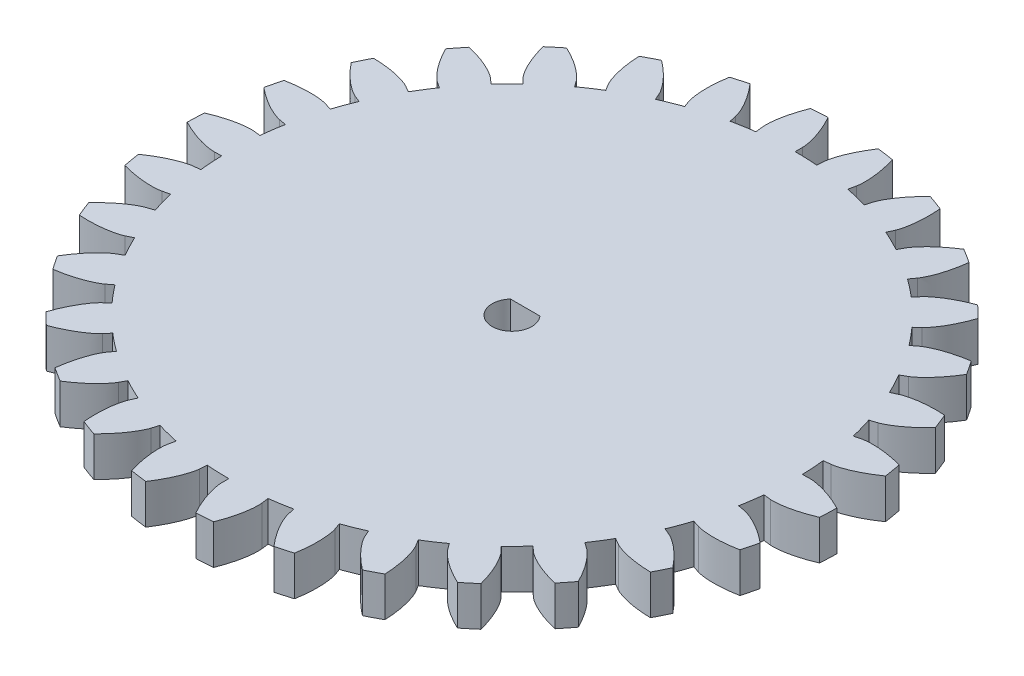
SolidWorks part; units mm, degrees
ref_plane "Front Plane" through (0, 0, 0) normal (0, 0, 1) x (1, 0, 0)
ref_plane "Top Plane" through (0, 0, 0) normal (0, 1, 0) x (1, 0, 0)
ref_plane "Right Plane" through (0, 0, 0) normal (1, 0, 0) x (0, 0, -1)
sketch "Reference attributes" plane through (0, 0, 0) normal (0, 1, 0) x (1, 0, 0)
  line L0 (0, 0) -> (30, 0) construction
  line L1 (0, -10) -> (1.56, -10) construction
  line L2 (0, 0) -> (28.9778, 7.7646) construction
  line L3 (0, 0) -> (28.1908, 10.2606) construction
  dimension "Teeth" = 30
  dimension "Module" = 1.56
  dimension "D2" = 10
  dimension "Helix Angle" = 15
  dimension "Pressure angle" = 20
sketch "Gear billet" plane through (0, 0, 0) normal (0, 1, 0) x (1, 0, 0)
  circle A0 centre (0, 0) radius 24.96
  dimension "OuterDi" = 49.92
extrude "Gear billet Extrude" add sketch "Gear billet" along normal blind 3
ref_plane "Opposite gear face" through (0, 3, 0) normal (0, 1, 0) x (1, 0, 0)
ref_point "Twist centre point top"
ref_point "Twist centre point bottom"
ref_axis "Axis" through (0, 3, 0) along (0, -1, 0)
sketch "Involute Profile" plane through (0, 3, 0) normal (0, 1, 0) x (1, 0, 0)
  line L0 (0, 0) -> (0, 21.9888) construction
  line L1 (0, 0) -> (1.7393, 21.9199) construction
  circle A0 centre (0, 0) radius 23.4
  circle A4 centre (0, 0) radius 21.9888 construction
  spline S0 degree 4 poles (0, 21.9888) (0, 22.0227) (-0.002, 22.0904) (-0.0183, 22.28) (-0.0768, 22.638) (-0.2134, 23.1773) (-0.4715, 23.897) (-0.8867, 24.788) (-1.4705, 25.7809) (-2.2091, 26.8084) (-3.0996, 27.8414) (-4.0685, 28.8009) (-5.1038, 29.688) (-6.2499, 30.5444) (-7.7363, 31.5083) (-9.5978, 32.5098) (-11.8594, 33.4668) (-14.465, 34.2773) (-17.1335, 34.8452) (-19.8405, 35.1813) (-22.5656, 35.2961) (-25.2912, 35.1997) (-27.663, 34.9395) (-29.6787, 34.5969) (-31.3427, 34.2349) (-32.4991, 33.942) (-33.4813, 33.6643) (-34.2972, 33.414) (-34.9416, 33.2053) (-35.5928, 32.9818) (-36.2216, 32.756) (-36.8226, 32.5279) (-37.3087, 32.3371) (-37.8607, 32.1112) (-38.2165, 31.9615) (-38.789, 31.7141) (-39.2308, 31.5139) (-39.7658, 31.2673) (-40.2388, 31.0393) (-40.7468, 30.7895) (-41.2252, 30.5448) (-41.5991, 30.3497) (-41.8363, 30.2223) (-41.9593, 30.1561) knots 0 0 0 0 0 0.002802 0.005604 0.015718 0.02996 0.048734 0.068727 0.096889 0.125051 0.153212 0.181374 0.209535 0.237696 0.271429 0.327752 0.384075 0.440398 0.496721 0.553044 0.609367 0.66569 0.722013 0.750174 0.778336 0.806497 0.820578 0.834659 0.84874 0.86282 0.876901 0.890982 0.900036 0.909091 0.920455 0.931818 0.943182 0.954545 0.965909 0.977273 0.988636 1 1 1 1 1 construction
  spline S1 degree 4 poles (0, 21.9888) (0, 22.0227) (-0.002, 22.0904) (-0.0183, 22.28) (-0.0768, 22.638) (-0.2134, 23.1773) (-0.4715, 23.897) (-0.8867, 24.788) (-1.4705, 25.7809) (-2.2091, 26.8084) (-3.0996, 27.8414) (-4.0685, 28.8009) (-5.1038, 29.688) (-6.2499, 30.5444) (-7.7363, 31.5083) (-9.5978, 32.5098) (-11.8594, 33.4668) (-14.465, 34.2773) (-17.1335, 34.8452) (-19.8405, 35.1813) (-22.5656, 35.2961) (-25.2912, 35.1997) (-27.663, 34.9395) (-29.6787, 34.5969) (-31.3427, 34.2349) (-32.4991, 33.942) (-33.4813, 33.6643) (-34.2972, 33.414) (-34.9416, 33.2053) (-35.5928, 32.9818) (-36.2216, 32.756) (-36.8226, 32.5279) (-37.3087, 32.3371) (-37.7167, 32.1701) (-37.9021, 32.0931) (-37.9939, 32.0546) knots 0 0 0 0 0 0.002802 0.005604 0.015718 0.02996 0.048734 0.068727 0.096889 0.125051 0.153212 0.181374 0.209535 0.237696 0.271429 0.327752 0.384075 0.440398 0.496721 0.553044 0.609367 0.66569 0.722013 0.750174 0.778336 0.806497 0.820578 0.834659 0.84874 0.86282 0.876901 0.890982 0.900036 0.909091 0.909091 0.909091 0.909091 0.909091
  spline S2 degree 4 poles (1.7393, 21.9199) (1.742, 21.9537) (1.7493, 22.0211) (1.7806, 22.2087) (1.8672, 22.561) (2.046, 23.0878) (2.3602, 23.7848) (2.8446, 24.6402) (3.5051, 25.5838) (4.3226, 26.5496) (5.2921, 27.509) (6.3339, 28.3888) (7.4361, 29.1913) (8.6463, 29.9544) (10.2043, 30.7977) (12.1392, 31.6487) (14.4694, 32.4239) (17.131, 33.0257) (19.836, 33.3808) (22.5612, 33.5017) (25.2867, 33.4006) (27.9962, 33.0889) (30.34, 32.6419) (32.3223, 32.141) (33.9524, 31.6485) (35.082, 31.2651) (36.0392, 30.9106) (36.8327, 30.5965) (37.4586, 30.3374) (38.0901, 30.0632) (38.699, 29.7884) (39.2801, 29.5134) (39.7496, 29.2848) (40.282, 29.0159) (40.6248, 28.8385) (41.176, 28.5466) (41.6005, 28.3121) (42.1144, 28.0239) (42.5679, 27.7593) (43.0545, 27.4701) (43.5121, 27.1883) (43.8694, 26.9642) (44.0957, 26.8185) (44.2131, 26.7428) knots 0 0 0 0 0 0.002802 0.005604 0.015718 0.02996 0.048734 0.068727 0.096889 0.125051 0.153212 0.181374 0.209535 0.237696 0.271429 0.327752 0.384075 0.440398 0.496721 0.553044 0.609367 0.66569 0.722013 0.750174 0.778336 0.806497 0.820578 0.834659 0.84874 0.86282 0.876901 0.890982 0.900036 0.909091 0.920455 0.931818 0.943182 0.954545 0.965909 0.977273 0.988636 1 1 1 1 1 construction
  spline S3 degree 4 poles (1.7393, 21.9199) (1.742, 21.9537) (1.7493, 22.0211) (1.7806, 22.2087) (1.8672, 22.561) (2.046, 23.0878) (2.3602, 23.7848) (2.8446, 24.6402) (3.5051, 25.5838) (4.3226, 26.5496) (5.2921, 27.509) (6.3339, 28.3888) (7.4361, 29.1913) (8.6463, 29.9544) (10.2043, 30.7977) (12.1392, 31.6487) (14.4694, 32.4239) (17.131, 33.0257) (19.836, 33.3808) (22.5612, 33.5017) (25.2867, 33.4006) (27.9962, 33.0889) (30.34, 32.6419) (32.3223, 32.141) (33.9524, 31.6485) (35.082, 31.2651) (36.0392, 30.9106) (36.8327, 30.5965) (37.4586, 30.3374) (38.0901, 30.0632) (38.699, 29.7884) (39.2801, 29.5134) (39.7496, 29.2848) (40.1431, 29.086) (40.3219, 28.9946) (40.4103, 28.9489) knots 0 0 0 0 0 0.002802 0.005604 0.015718 0.02996 0.048734 0.068727 0.096889 0.125051 0.153212 0.181374 0.209535 0.237696 0.271429 0.327752 0.384075 0.440398 0.496721 0.553044 0.609367 0.66569 0.722013 0.750174 0.778336 0.806497 0.820578 0.834659 0.84874 0.86282 0.876901 0.890982 0.900036 0.909091 0.909091 0.909091 0.909091 0.909091
  point P6 (-0.3003, 23.3981)
  point P11 (2.1501, 23.301)
  dimension "BaseDi" = 43.9776
  dimension "Adjusted Reference Diameter" = 46.8
  dimension "Reference Circumferential pitch" = 2.4504
sketch "Tooth profile" plane through (0, 3, 0) normal (0, 1, 0) x (1, 0, 0)
  line L0 (0, 0) -> (0, 21.9888) construction
  line L1 (0, 0) -> (1.7393, 21.9199) construction
  line L2 (0, 0) -> (0, 21.9888)
  line L3 (0, 0) -> (1.7393, 21.9199)
  line L4 (-0.2, -5.0491) -> (-0.2, 21.9888) construction
  line L5 (-0.2, -5.0491) -> (1.9386, 21.9041) construction
  circle A0 centre (0, 0) radius 24.96 construction
  circle A1 centre (0, 0) radius 24.96
  circle A2 centre (0, 0) radius 21.45
  spline S0 degree 1 poles (-0.2, 21.9888) (-37.9165, 31.8702) knots 0 0 1 1 construction
  spline S1 degree 4 poles (999.1982, -17.1121) (-36.277, 17.6441) (-0.8293, 18.6178) (0.2518, 20.6259) (-0.0768, 22.638) (-0.2134, 23.1773) (-0.4715, 23.897) (-0.8867, 24.788) (-1.4705, 25.7809) (-2.2091, 26.8084) (-3.0996, 27.8414) (-4.0685, 28.8009) (-5.1038, 29.688) (-6.2499, 30.5444) (-7.7363, 31.5083) (-9.5978, 32.5098) (-11.8594, 33.4668) (-14.465, 34.2773) (-17.1335, 34.8452) (-19.8405, 35.1813) (-22.5656, 35.2961) (-25.2912, 35.1997) (-27.663, 34.9395) (-29.6787, 34.5969) (-31.3427, 34.2349) (-32.4991, 33.942) (-33.4813, 33.6643) (-34.2972, 33.414) (-34.9416, 33.2053) (-35.5928, 32.9818) (-36.2216, 32.756) (-36.8226, 32.5279) (-38.6811, 31.7987) (-42.1779, 30.2496) (-10.1825, 43.4984) (-959.7925, -355.2431) knots -0.138436 -0.138436 -0.138436 -0.138436 -0.138436 0.002802 0.005604 0.015718 0.02996 0.048734 0.068727 0.096889 0.125051 0.153212 0.181374 0.209535 0.237696 0.271429 0.327752 0.384075 0.440398 0.496721 0.553044 0.609367 0.66569 0.722013 0.750174 0.778336 0.806497 0.820578 0.834659 0.84874 0.86282 0.876901 0.890982 0.900036 1.039722 1.039722 1.039722 1.039722 1.039722 only from (0, 21.9888) to (-37.9939, 32.0546) construction
  spline S2 degree 4 poles (-997.4211, 61.976) (37.5589, 14.7194) (2.2993, 18.4939) (1.3805, 20.5812) (1.8672, 22.561) (2.046, 23.0878) (2.3602, 23.7848) (2.8446, 24.6402) (3.5051, 25.5838) (4.3226, 26.5496) (5.2921, 27.509) (6.3339, 28.3888) (7.4361, 29.1913) (8.6463, 29.9544) (10.2043, 30.7977) (12.1392, 31.6487) (14.4694, 32.4239) (17.131, 33.0257) (19.836, 33.3808) (22.5612, 33.5017) (25.2867, 33.4006) (27.9962, 33.0889) (30.34, 32.6419) (32.3223, 32.141) (33.9524, 31.6485) (35.082, 31.2651) (36.0392, 30.9106) (36.8327, 30.5965) (37.4586, 30.3374) (38.0901, 30.0632) (38.699, 29.7884) (39.2801, 29.5134) (41.0751, 28.6395) (44.4385, 26.8186) (13.5912, 42.5567) (928.6863, -430.0476) knots -0.138436 -0.138436 -0.138436 -0.138436 -0.138436 0.002802 0.005604 0.015718 0.02996 0.048734 0.068727 0.096889 0.125051 0.153212 0.181374 0.209535 0.237696 0.271429 0.327752 0.384075 0.440398 0.496721 0.553044 0.609367 0.66569 0.722013 0.750174 0.778336 0.806497 0.820578 0.834659 0.84874 0.86282 0.876901 0.890982 0.900036 1.039722 1.039722 1.039722 1.039722 1.039722 only from (1.7393, 21.9199) to (40.4103, 28.9489) construction
  spline S3 degree 1 poles (1.9386, 21.9041) (40.3186, 28.7712) knots 0 0 1 1 construction
  spline S4 degree 4 poles (0, 21.9888) (0, 22.0227) (-0.002, 22.0904) (-0.0183, 22.28) (-0.0768, 22.638) (-0.2134, 23.1773) (-0.4715, 23.897) (-0.8867, 24.788) (-1.4705, 25.7809) (-2.2091, 26.8084) (-3.0996, 27.8414) (-4.0685, 28.8009) (-5.1038, 29.688) (-6.2499, 30.5444) (-7.7363, 31.5083) (-9.5978, 32.5098) (-11.8594, 33.4668) (-14.465, 34.2773) (-17.1335, 34.8452) (-19.8405, 35.1813) (-22.5656, 35.2961) (-25.2912, 35.1997) (-27.663, 34.9395) (-29.6787, 34.5969) (-31.3427, 34.2349) (-32.4991, 33.942) (-33.4813, 33.6643) (-34.2972, 33.414) (-34.9416, 33.2053) (-35.5928, 32.9818) (-36.2216, 32.756) (-36.8226, 32.5279) (-37.3087, 32.3371) (-37.7167, 32.1701) (-37.9021, 32.0931) (-37.9939, 32.0546) knots 0 0 0 0 0 0.002802 0.005604 0.015718 0.02996 0.048734 0.068727 0.096889 0.125051 0.153212 0.181374 0.209535 0.237696 0.271429 0.327752 0.384075 0.440398 0.496721 0.553044 0.609367 0.66569 0.722013 0.750174 0.778336 0.806497 0.820578 0.834659 0.84874 0.86282 0.876901 0.890982 0.900036 0.909091 0.909091 0.909091 0.909091 0.909091
  spline S5 degree 4 poles (1.7393, 21.9199) (1.742, 21.9537) (1.7493, 22.0211) (1.7806, 22.2087) (1.8672, 22.561) (2.046, 23.0878) (2.3602, 23.7848) (2.8446, 24.6402) (3.5051, 25.5838) (4.3226, 26.5496) (5.2921, 27.509) (6.3339, 28.3888) (7.4361, 29.1913) (8.6463, 29.9544) (10.2043, 30.7977) (12.1392, 31.6487) (14.4694, 32.4239) (17.131, 33.0257) (19.836, 33.3808) (22.5612, 33.5017) (25.2867, 33.4006) (27.9962, 33.0889) (30.34, 32.6419) (32.3223, 32.141) (33.9524, 31.6485) (35.082, 31.2651) (36.0392, 30.9106) (36.8327, 30.5965) (37.4586, 30.3374) (38.0901, 30.0632) (38.699, 29.7884) (39.2801, 29.5134) (39.7496, 29.2848) (40.1431, 29.086) (40.3219, 28.9946) (40.4103, 28.9489) knots 0 0 0 0 0 0.002802 0.005604 0.015718 0.02996 0.048734 0.068727 0.096889 0.125051 0.153212 0.181374 0.209535 0.237696 0.271429 0.327752 0.384075 0.440398 0.496721 0.553044 0.609367 0.66569 0.722013 0.750174 0.778336 0.806497 0.820578 0.834659 0.84874 0.86282 0.876901 0.890982 0.900036 0.909091 0.909091 0.909091 0.909091 0.909091
  spline S6 degree 3 poles (-37.9165, 31.8702) (-34.5637, 33.2771) (-29.2333, 34.7703) (-21.9373, 35.188) (-16.4816, 34.6386) (-11.2068, 33.1415) (-7.1485, 31.0333) (-4.2854, 28.7886) (-2.4032, 26.8185) (-1.144, 24.9283) (-0.5176, 23.4861) (-0.2764, 22.622) (-0.2, 22.203) (-0.2, 21.9888) knots 0 0 0 0 0.227273 0.340909 0.454545 0.568182 0.681818 0.738636 0.795455 0.852273 0.880682 0.894886 0.909091 0.909091 0.909091 0.909091 construction
  spline S7 degree 3 poles (1.9386, 21.9041) (1.9556, 22.1176) (2.0649, 22.5293) (2.3737, 23.3716) (3.1122, 24.7598) (4.5169, 26.5444) (6.5491, 28.3595) (9.5808, 30.3707) (13.7931, 32.1512) (19.1698, 33.2264) (24.6519, 33.3426) (31.892, 32.3491) (37.0876, 30.439) (40.3186, 28.7712) knots 0 0 0 0 0.014205 0.028409 0.056818 0.113636 0.170455 0.227273 0.340909 0.454545 0.568182 0.681818 0.909091 0.909091 0.909091 0.909091 construction
  dimension "RootDi" = 42.9
  dimension "Offset" = 0.2
extrude "Cut tooth profile" cut sketch "Tooth profile" against normal up to next contours A1 region at (0.9288, 3, -23.4481)
sketch "Tooth profile OFFSET" plane through (0, 3, 0) normal (0, 1, 0) x (1, 0, 0)
  line L4 (-0.1, -2.5246) -> (-0.1, 21.9888)
  line L5 (1.839, 21.912) -> (-0.1, -2.5246)
  line L6 (-0.1, -2.5246) -> (-0.1, 21.9888)
  line L7 (1.839, 21.912) -> (-0.1, -2.5246)
  circle A3 centre (0, 0) radius 24.96 construction
  circle A4 centre (0, 0) radius 24.96
  circle A6 centre (0, 0) radius 21.35
  circle A7 centre (0, 0) radius 21.35
  spline S4 degree 3 poles (1814.9164, -893.4497) (11.2099, 41.5431) (47.43, 25.2825) (39.9677, 29.0624) (39.857, 29.118) (39.5391, 29.276) (39.3439, 29.3707) (38.9333, 29.5665) (38.7217, 29.6655) (38.306, 29.8557) (38.0998, 29.9479) (37.053, 30.4066) (36.203, 30.7469) (33.6257, 31.6798) (31.8646, 32.1874) (28.2886, 32.9442) (26.4731, 33.1936) (22.8249, 33.4041) (20.9921, 33.3652) (17.3608, 32.9668) (15.562, 32.6072) (12.0726, 31.5326) (10.3808, 30.8175) (8.0112, 29.4496) (7.2497, 28.9445) (5.8069, 27.8305) (5.1252, 27.2218) (3.8784, 25.8951) (3.3115, 25.1772) (2.6029, 24.0143) (2.3903, 23.6123) (2.1256, 22.9877) (2.0464, 22.776) (1.9476, 22.4534) (1.918, 22.3451) (0.4034, 15.6952) (12.5067, 9.1011) (1949.2716, 476.354) knots -0.54262 -0.54262 -0.54262 -0.54262 0.007812 0.007812 0.015625 0.015625 0.03125 0.03125 0.046875 0.046875 0.0625 0.0625 0.125 0.125 0.25 0.25 0.375 0.375 0.5 0.5 0.625 0.625 0.75 0.75 0.8125 0.8125 0.875 0.875 0.9375 0.9375 0.96875 0.96875 0.984375 0.984375 0.992187 0.992187 1.461818 1.461818 1.461818 1.461818 only from (40.3645, 28.8601) to (1.839, 21.912)
  spline S5 degree 3 poles (-1905.5571, 629.0682) (-11.748, 10.0617) (0.8394, 15.6778) (-0.1445, 22.4268) (-0.1655, 22.5371) (-0.2385, 22.8665) (-0.3007, 23.0838) (-0.5151, 23.7274) (-0.6952, 24.1449) (-1.3097, 25.3602) (-1.818, 26.1208) (-2.956, 27.5419) (-3.5873, 28.2027) (-4.9375, 29.4272) (-5.6567, 29.991) (-7.9107, 31.542) (-9.5406, 32.3887) (-12.9341, 33.736) (-14.6989, 34.2367) (-18.2872, 34.9211) (-20.1112, 35.1048) (-23.7646, 35.1836) (-25.5942, 35.0786) (-29.2188, 34.607) (-31.0145, 34.2403) (-33.6576, 33.5142) (-34.5318, 33.2422) (-35.6116, 32.8677) (-35.8244, 32.7921) (-36.2539, 32.6354) (-36.4727, 32.5534) (-36.8975, 32.3907) (-37.0995, 32.3118) (-37.429, 32.1793) (-37.5437, 32.1327) (-45.2816, 28.9549) (-7.889, 42.2995) (-1879.8826, -747.087) knots -0.461823 -0.461823 -0.461823 -0.461823 0.007812 0.007812 0.015625 0.015625 0.03125 0.03125 0.0625 0.0625 0.125 0.125 0.1875 0.1875 0.25 0.25 0.375 0.375 0.5 0.5 0.625 0.625 0.75 0.75 0.875 0.875 0.9375 0.9375 0.953125 0.953125 0.96875 0.96875 0.984375 0.984375 0.992188 0.992188 1.542618 1.542618 1.542618 1.542618 only from (-0.1, 21.9888) to (-37.9552, 31.9624)
  spline S6 degree 3 poles (40.3645, 28.8601) (40.2722, 28.9077) (40.1765, 28.9566) (39.9677, 29.0624) (39.857, 29.118) (39.5391, 29.276) (39.3439, 29.3707) (38.9333, 29.5665) (38.7217, 29.6655) (38.306, 29.8557) (38.0998, 29.9479) (37.053, 30.4066) (36.203, 30.7469) (33.6257, 31.6798) (31.8646, 32.1874) (28.2886, 32.9442) (26.4731, 33.1936) (22.8249, 33.4041) (20.9921, 33.3652) (17.3608, 32.9668) (15.562, 32.6072) (12.0726, 31.5326) (10.3808, 30.8175) (8.0112, 29.4496) (7.2497, 28.9445) (5.8069, 27.8305) (5.1252, 27.2218) (3.8784, 25.8951) (3.3115, 25.1772) (2.6029, 24.0143) (2.3903, 23.6123) (2.1256, 22.9877) (2.0464, 22.776) (1.9476, 22.4534) (1.918, 22.3451) (1.8684, 22.1275) (1.8474, 22.0187) (1.839, 21.912) knots 0 0 0 0 0.007812 0.007812 0.015625 0.015625 0.03125 0.03125 0.046875 0.046875 0.0625 0.0625 0.125 0.125 0.25 0.25 0.375 0.375 0.5 0.5 0.625 0.625 0.75 0.75 0.8125 0.8125 0.875 0.875 0.9375 0.9375 0.96875 0.96875 0.984375 0.984375 0.992187 0.992187 1 1 1 1
  spline S7 degree 3 poles (-0.1, 21.9888) (-0.1, 22.0958) (-0.1123, 22.206) (-0.1445, 22.4268) (-0.1655, 22.5371) (-0.2385, 22.8665) (-0.3007, 23.0838) (-0.5151, 23.7274) (-0.6952, 24.1449) (-1.3097, 25.3602) (-1.818, 26.1208) (-2.956, 27.5419) (-3.5873, 28.2027) (-4.9375, 29.4272) (-5.6567, 29.991) (-7.9107, 31.542) (-9.5406, 32.3887) (-12.9341, 33.736) (-14.6989, 34.2367) (-18.2872, 34.9211) (-20.1112, 35.1048) (-23.7646, 35.1836) (-25.5942, 35.0786) (-29.2188, 34.607) (-31.0145, 34.2403) (-33.6576, 33.5142) (-34.5318, 33.2422) (-35.6116, 32.8677) (-35.8244, 32.7921) (-36.2539, 32.6354) (-36.4727, 32.5534) (-36.8975, 32.3907) (-37.0995, 32.3118) (-37.429, 32.1793) (-37.5437, 32.1327) (-37.7603, 32.0437) (-37.8595, 32.0026) (-37.9552, 31.9624) knots 0 0 0 0 0.007812 0.007812 0.015625 0.015625 0.03125 0.03125 0.0625 0.0625 0.125 0.125 0.1875 0.1875 0.25 0.25 0.375 0.375 0.5 0.5 0.625 0.625 0.75 0.75 0.875 0.875 0.9375 0.9375 0.953125 0.953125 0.96875 0.96875 0.984375 0.984375 0.992188 0.992188 1 1 1 1
  line M3 (0, 21.45) -> (0, 21.9888)
  spline M4 degree 4 poles (0, 21.9888) (0, 22.0227) (-0.002, 22.0904) (-0.0183, 22.28) (-0.0768, 22.638) (-0.2134, 23.1773) (-0.4715, 23.897) (-0.8867, 24.788) (-1.4705, 25.7809) (-2.2091, 26.8084) (-3.0996, 27.8414) (-4.0685, 28.8009) (-5.1038, 29.688) (-6.2499, 30.5444) (-7.7363, 31.5083) (-9.5978, 32.5098) (-11.8594, 33.4668) (-14.465, 34.2773) (-17.1335, 34.8452) (-19.8405, 35.1813) (-22.5656, 35.2961) (-25.2912, 35.1997) (-27.663, 34.9395) (-29.6787, 34.5969) (-31.3427, 34.2349) (-32.4991, 33.942) (-33.4813, 33.6643) (-34.2972, 33.414) (-34.9416, 33.2053) (-35.5928, 32.9818) (-36.2216, 32.756) (-36.8226, 32.5279) (-37.3087, 32.3371) (-37.7167, 32.1701) (-37.9021, 32.0931) (-37.9939, 32.0546) knots 0 0 0 0 0 0.002802 0.005604 0.015718 0.02996 0.048734 0.068727 0.096889 0.125051 0.153212 0.181374 0.209535 0.237696 0.271429 0.327752 0.384075 0.440398 0.496721 0.553044 0.609367 0.66569 0.722013 0.750174 0.778336 0.806497 0.820578 0.834659 0.84874 0.86282 0.876901 0.890982 0.900036 0.909091 0.909091 0.909091 0.909091 0.909091 only from (0, 21.9888) to (-0.9929, 24.9402)
  arc M5 (-0.9929, 24.9402) -> (2.9625, 24.7836) centre (0, 0) ccw
  spline M6 degree 4 poles (40.4103, 28.9489) (40.3219, 28.9946) (40.1431, 29.086) (39.7496, 29.2848) (39.2801, 29.5134) (38.699, 29.7884) (38.0901, 30.0632) (37.4586, 30.3374) (36.8327, 30.5965) (36.0392, 30.9106) (35.082, 31.2651) (33.9524, 31.6485) (32.3223, 32.141) (30.34, 32.6419) (27.9962, 33.0889) (25.2867, 33.4006) (22.5612, 33.5017) (19.836, 33.3808) (17.131, 33.0257) (14.4694, 32.4239) (12.1392, 31.6487) (10.2043, 30.7977) (8.6463, 29.9544) (7.4361, 29.1913) (6.3339, 28.3888) (5.2921, 27.509) (4.3226, 26.5496) (3.5051, 25.5838) (2.8446, 24.6402) (2.3602, 23.7848) (2.046, 23.0878) (1.8672, 22.561) (1.7806, 22.2087) (1.7493, 22.0211) (1.742, 21.9537) (1.7393, 21.9199) knots 0 0 0 0 0 0.009054 0.018109 0.03219 0.04627 0.060351 0.074432 0.088513 0.102594 0.130755 0.158916 0.187078 0.243401 0.299724 0.356047 0.41237 0.468693 0.525016 0.581339 0.637662 0.671395 0.699556 0.727717 0.755879 0.78404 0.812202 0.840364 0.860357 0.879131 0.893373 0.903487 0.906289 0.909091 0.909091 0.909091 0.909091 0.909091 only from (2.9625, 24.7836) to (1.7393, 21.9199)
  line M7 (1.7393, 21.9199) -> (1.6967, 21.3828)
  arc M8 (1.6967, 21.3828) -> (0, 21.45) centre (0, 0) ccw
  dimension "Offset" = 0.1
  dimension "D2" = 0.1
extrude "Cut Tooth profile OFFSET" [suppressed] cut sketch "Tooth profile OFFSET" against normal up to surface (10 mm away) contours S7 L6 A7 L7 S6 A4 M6 M7 M8 M3 M4 M5 up to face at (0.5914, 0, -14.9312)
sketch "Tangent meshing reference" plane through (0, 3, 0) normal (0, 1, 0) x (1, 0, 0)
  circle A0 centre (0, 0) radius 23.4 construction
  circle A1 centre (0, 0) radius 23.4
sketch "Gear ratio reference" plane through (0, 3, 0) normal (0, 1, 0) x (1, 0, 0)
  circle A0 centre (0, 0) radius 23.4
  dimension "Reference diameter" = 46.8
pattern_circular "Duplicate teeth" count 30 over 360 about axis through (0, 3, 0) along (0, -1, 0) of "Cut tooth profile"
other "Twist Left" [suppressed] parameters "D0"=1.968
other "Twist Right" [suppressed] parameters "D0"=1.968
mirror "Herringbone Mirror" [suppressed] about plane through (0, 3, 0) normal (0, 1, 0) of bodies 259
sketch "Sketch1" plane through (0, 3, 0) normal (0, 1, 0) x (1, 0, 0)
  line L0 (-1.118, 1) -> (1.118, 1)
  arc A0 (-1.118, 1) -> (1.118, 1) centre (0, 0) ccw
  point P5 (0, 0)
  dimension "D1" = 3
  dimension "D2" = 2.5
extrude "Cut-Extrude1" cut sketch "Sketch1" against normal through all
equation "\"D1@Duplicate teeth\"=\"Teeth@Reference attributes\""
equation "\"twist\"= \"suppressed\""
equation "\"D2@Tooth profile OFFSET\"=\"Offset@Tooth profile OFFSET\""
